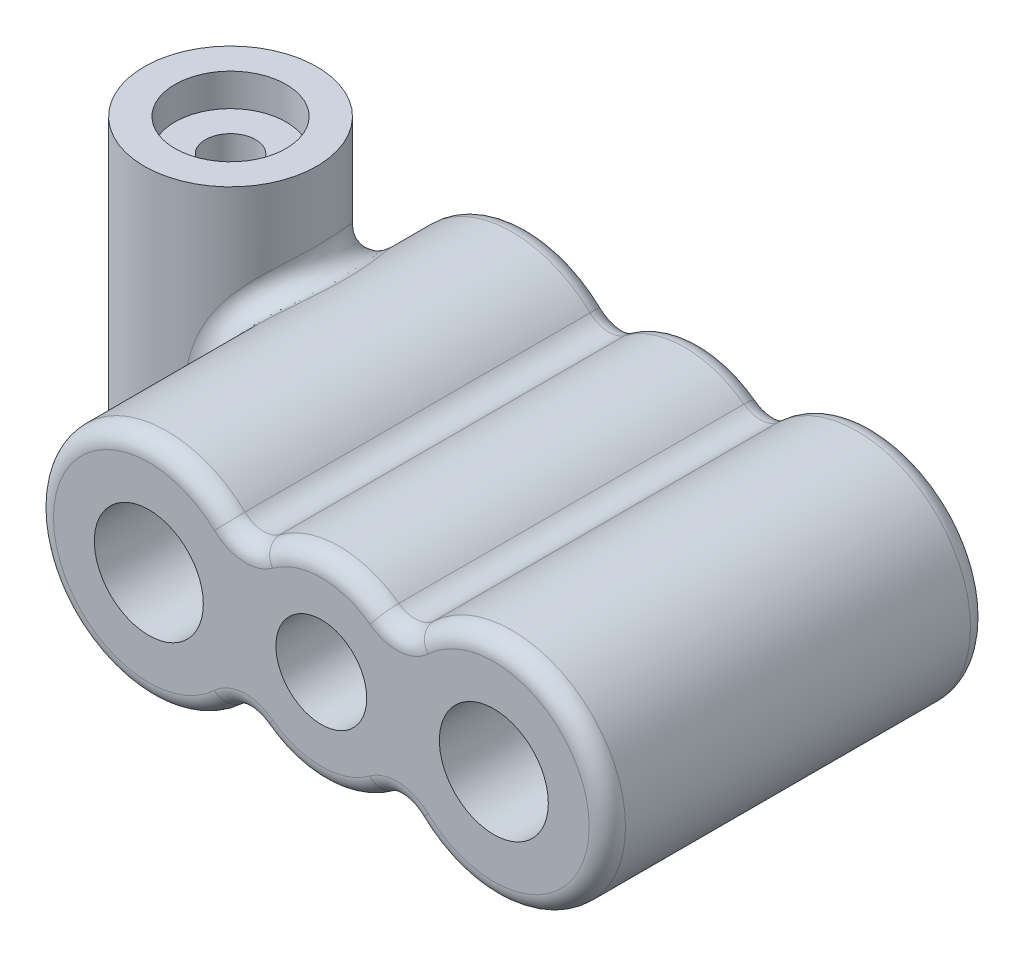
SolidWorks part; units mm, degrees
ref_plane "Front Plane" through (0, 0, 0) normal (0, 0, 1) x (1, 0, 0)
ref_plane "Top Plane" through (0, 0, 0) normal (0, 1, 0) x (1, 0, 0)
ref_plane "Right Plane" through (0, 0, 0) normal (1, 0, 0) x (0, 0, -1)
sketch "Sketch1" plane through (0, 0, 0) normal (0, 0, 1) x (1, 0, 0)
  line L0 (0, 0) -> (38, 0) construction
  arc A0 (10.4276, 6.8931) -> (10.4276, -6.8931) centre (0, 0) ccw
  arc A1 (10.4276, -6.8931) -> (27.5724, -6.8931) centre (19, 0) ccw
  arc A2 (27.5724, -6.8931) -> (27.5724, 6.8931) centre (38, 0) ccw
  arc A3 (27.5724, 6.8931) -> (10.4276, 6.8931) centre (19, 0) ccw
  dimension "D1" = 22
  dimension "D2" = 25
  dimension "D3" = 38
extrude "Boss-Extrude1" add sketch "Sketch1" along normal blind 42
sketch "Sketch2" plane through (0, 0, 0) normal (0, 1, 0) x (1, 0, 0)
  line L1 (10.4276, 0) -> (-12.5, 0) construction
  line L2 (19, -42) -> (19, 0) construction
  circle A0 centre (-19, -14) radius 9.5
  dimension "D1" = 19
  dimension "D3" = 38
  dimension "D2" = 14
extrude "Boss-Extrude2" add sketch "Sketch2" along normal mid plane 40
hole_wizard "Ø12.0 (12) Diameter Hole1" positions "Sketch4" profile "Sketch3" hole size "Ø12.0" standard "ANSI Metric" end condition through all
sketch "Sketch4" plane through (0, 0, 42) normal (0, 0, 1) x (1, 0, 0)
  point P0 (0, 0)
  point P3 (38, 0)
sketch "Sketch3" plane through (0, 0, 42) normal (1, 0, 0) x (0, -1, 0)
  line L0 (0, 0) -> (0, 42)
  line L1 (0, 42) -> (6, 42)
  line L2 (6, 42) -> (6, 0)
  line L5 (6, 0) -> (0, 0)
  line L11 (0, -6.35) -> (0, 107.95) construction
  dimension "Thru Hole Dia." = 12
  dimension "Thru Hole Depth" = 42
hole_wizard "Ø10.0 (10) Diameter Hole1" positions "Sketch7" profile "Sketch6" hole size "Ø10.0" standard "ANSI Metric" end condition through all
sketch "Sketch7" plane through (0, 0, 42) normal (0, 0, 1) x (1, 0, 0)
  point P0 (19, 0)
sketch "Sketch6" plane through (19, 0, 42) normal (1, 0, 0) x (0, -1, 0)
  line L0 (0, 0) -> (0, 42)
  line L1 (0, 42) -> (5, 42)
  line L2 (5, 42) -> (5, 0)
  line L5 (5, 0) -> (0, 0)
  line L11 (0, -6.35) -> (0, 107.95) construction
  dimension "Thru Hole Dia." = 10
  dimension "Thru Hole Depth" = 42
hole_wizard "CBORE for M5 Hex Head Bolt1" positions "Sketch9" profile "Sketch8" counterbore size "M5" standard "ANSI Metric" end condition through all
sketch "Sketch9" plane through (0, 20, 0) normal (0, 1, 0) x (1, 0, 0)
  point P0 (-19, -14)
sketch "Sketch8" plane through (-19, 20, 14) normal (1, 0, 0) x (0, 0, 1)
  line L0 (0, 0) -> (0, 40)
  line L1 (0, 40) -> (2.75, 40)
  line L3 (2.75, 40) -> (2.75, 3.58)
  line L4 (2.75, 3.58) -> (6.12, 3.58)
  line L5 (6.12, 3.58) -> (6.12, 0)
  line L7 (6.12, 0) -> (0, 0)
  line L11 (0, -6.35) -> (0, 107.95) construction
  dimension "Thru Hole Dia." = 5.5
  dimension "Thru Hole Depth" = 40
  dimension "C'Bore Dia." = 12.24
  dimension "C'Bore Depth" = 3.58
fillet "Fillet1" radius 3 4 edges at (10.4276, -6.8931, 21) (27.5724, -6.8931, 21) (27.5724, 6.8931, 21) (10.4276, 6.8931, 21)
fillet "Fillet2" radius 2 17 edges at (10.4831, 8.2536, 0) (19, 11, 0) (27.5169, 8.2536, 0) (50.5, 0, 0) (27.5169, -8.2536, 0) (19, -11, 0) (10.4831, -8.2536, 0) (10.4831, 8.2536, 42) (19, 11, 42) (27.5169, 8.2536, 42) (50.5, 0, 42) (27.5169, -8.2536, 42) (19, -11, 42) (10.4831, -8.2536, 42) (-12.3593, -1.8704, 7.2066) (-12.5, 0, 0) (-12.5, 0, 42)
